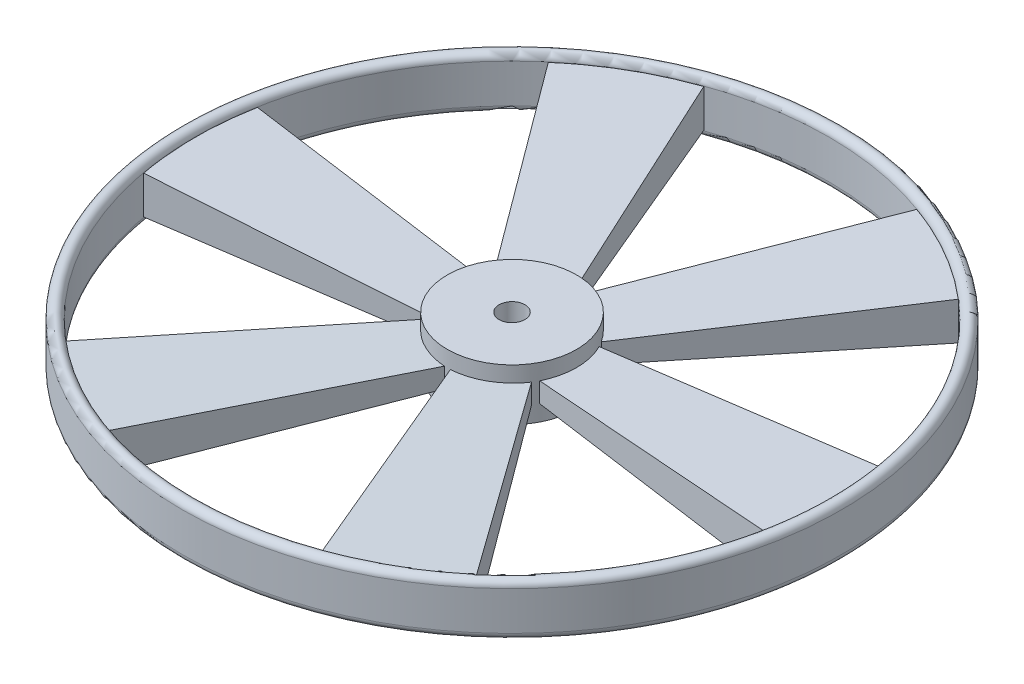
SolidWorks part; units mm, degrees
ref_plane "Front Plane" through (0, 0, 0) normal (0, 0, 1) x (1, 0, 0)
ref_plane "Top Plane" through (0, 0, 0) normal (0, 1, 0) x (1, 0, 0)
ref_plane "Right Plane" through (0, 0, 0) normal (1, 0, 0) x (0, 0, -1)
sketch "Sketch1" plane through (0, 0, 0) normal (0, 0, 1) x (1, 0, 0)
  line L0 (25, 1.5) -> (25, -1.5) construction
  line L1 (25.5, 1.5) -> (25.5, -1.5)
  line L2 (24.5, 1.5) -> (24.5, -1.5)
  line L3 (0, 4.2582) -> (0, -6.6402) construction
  arc A0 (25.5, 1.5) -> (24.5, 1.5) centre (25, 1.5) ccw
  arc A1 (24.5, -1.5) -> (25.5, -1.5) centre (25, -1.5) ccw
  point P2 (25, 0)
  dimension "D2" = 0.5
  dimension "D3" = 25
  dimension "D1" = 3
revolve "Revolve1" add sketch "Sketch1" angle 360 about L3
sketch "Sketch2" plane through (0, 0, 0) normal (0, 1, 0) x (1, 0, 0)
  circle A0 centre (0, 0) radius 5
  dimension "D1" = 10
extrude "Boss-Extrude1" add sketch "Sketch2" against normal blind 2 and the other way blind 2 separate body
ref_plane "Plane1" through (4, 0, 0) normal (1, 0, 0) x (0, 0, -1)
ref_plane "Plane2" through (25, 0, 0) normal (1, 0, 0) x (0, 0, -1)
sketch "Sketch3" plane through (4, 0, 0) normal (1, 0, 0) x (0, 0, -1)
  line L1 (2.25, -0.75) -> (-2.25, -0.75)
  line L2 (2.25, -0.75) -> (2.25, 0.75)
  line L3 (2.25, 0.75) -> (-2.25, 0.75)
  line L4 (-2.25, -0.75) -> (-2.25, 0.75)
  line L5 (2.25, -0.75) -> (-2.25, 0.75) construction
  line L6 (2.25, 0.75) -> (-2.25, -0.75) construction
  point P0 (0, 0)
  dimension "D1" = 1.5
  dimension "D2" = 4.5
sketch "Sketch4" plane through (25, 0, 0) normal (1, 0, 0) x (0, 0, -1)
  line L1 (4.5, -1.5) -> (-4.5, -1.5)
  line L2 (4.5, -1.5) -> (4.5, 1.5)
  line L3 (4.5, 1.5) -> (-4.5, 1.5)
  line L4 (-4.5, -1.5) -> (-4.5, 1.5)
  line L5 (4.5, -1.5) -> (-4.5, 1.5) construction
  line L6 (4.5, 1.5) -> (-4.5, -1.5) construction
  point P0 (0, 0)
  dimension "D1" = 3
  dimension "D2" = 9
loft "Loft1" add profiles "Sketch4", "Sketch3"
pattern_circular "CirPattern1" count 6 over 360 about axis through (0, 2, 0) along (0, 1, 0) of "Loft1"
sketch "Sketch5" plane through (0, 2, 0) normal (0, 1, 0) x (1, 0, 0)
  circle A0 centre (0, 0) radius 1
  dimension "D1" = 2
extrude "Cut-Extrude1" cut sketch "Sketch5" against normal blind 3
